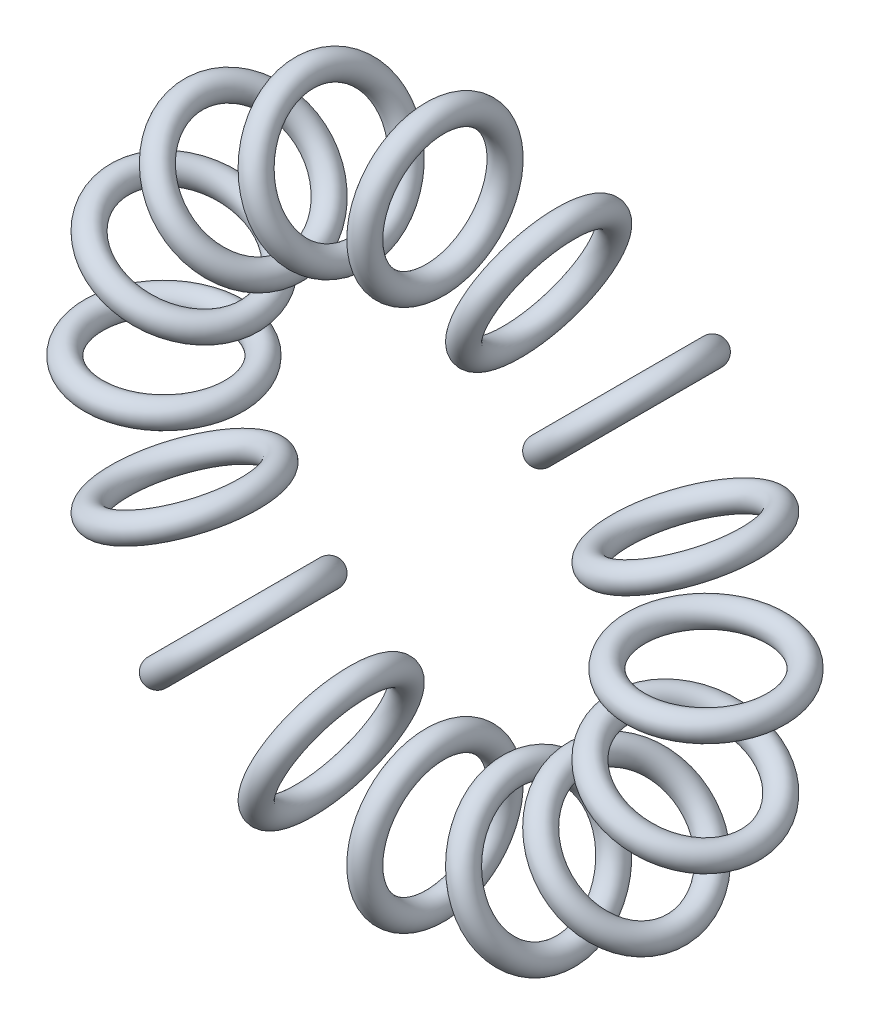
SolidWorks part; units mm, degrees
ref_plane "Plano frontal" through (0, 0, 0) normal (0, 0, 1) x (1, 0, 0)
ref_plane "Plano superior" through (0, 0, 0) normal (0, 1, 0) x (1, 0, 0)
ref_plane "Plano direito" through (0, 0, 0) normal (1, 0, 0) x (0, 0, -1)
sketch "Esboço1" plane through (0, 0, 0) normal (0, 0, 1) x (1, 0, 0)
  circle A1 centre (0, 15.75) radius 1
ref_axis "Eixo1" through (0, 0, 4.638) along (0, 0, -1)
sketch "Esboço3" plane through (0, 0, 0) normal (0, 0, 1) x (1, 0, 0)
  line L1 (0, 21.25) -> (4.4046, 21.25)
revolve "Revolução1" add sketch "Esboço1" angle 360 about L1
pattern_circular "CirPattern1" count 16 over 360 about axis through (0, 0, 4.638) along (0, 0, -1) of bodies 117
ref_axis "Eixo2" through (4.4046, 21.25, 0) along (-1, 0, 0)
